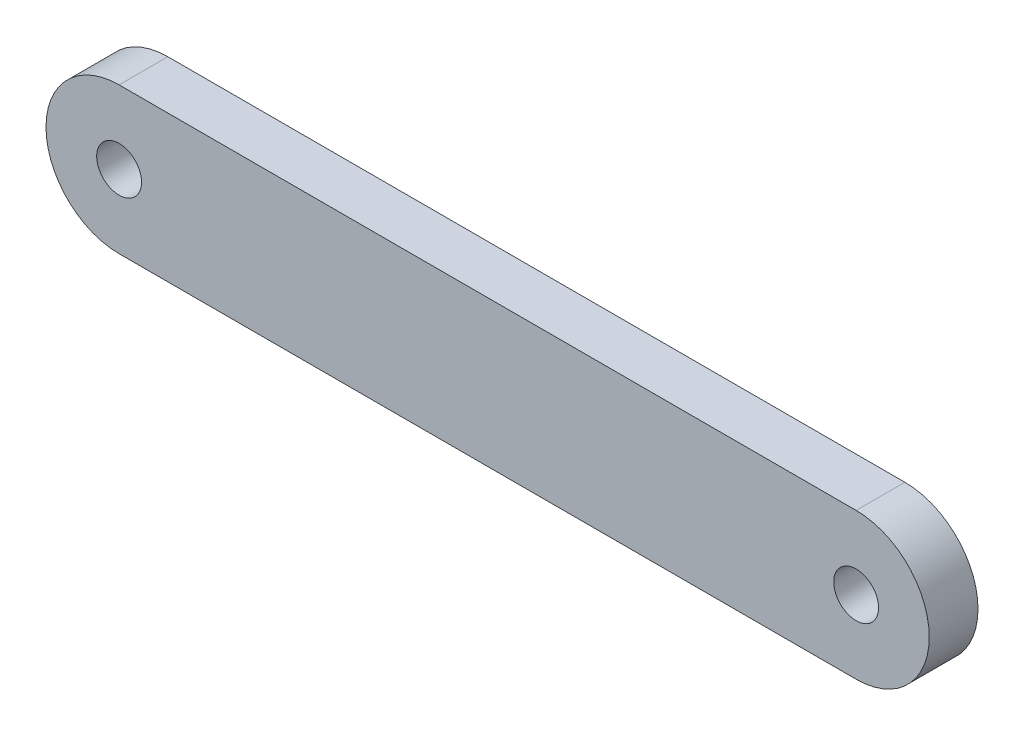
SolidWorks part; units mm, degrees
ref_plane "前视基准面" through (0, 0, 0) normal (0, 0, 1) x (1, 0, 0)
ref_plane "上视基准面" through (0, 0, 0) normal (0, 1, 0) x (1, 0, 0)
ref_plane "右视基准面" through (0, 0, 0) normal (1, 0, 0) x (0, 0, -1)
other "Configuration Table"
sketch "草图1" plane through (0, 0, 0) normal (0, 0, 1) x (1, 0, 0)
  line L1 (-37.8, 7.5) -> (37.8, 7.5)
  line L3 (-37.8, -7.5) -> (37.8, -7.5)
  line L5 (-37.8, 7.5) -> (37.8, -7.5) construction
  line L6 (-37.8, -7.5) -> (37.8, 7.5) construction
  arc A0 (-37.8, 7.5) -> (-37.8, -7.5) centre (-37.8, 0) ccw
  arc A1 (37.8, 7.5) -> (37.8, -7.5) centre (37.8, 0) cw
  circle A2 centre (-37.8, 0) radius 2.3
  circle A3 centre (37.8, 0) radius 2.3
  point P0 (0, 0)
  dimension "D1" = 4.6
  dimension "D2" = 4.6
  dimension "D3" = 75.6
  dimension "D4" = 15
extrude "凸台-拉伸1" add sketch "草图1" along normal blind 5
equation "\"fi\"=4.6"
equation "\"D1@草图1\"=\"fi\""
equation "\"D2@草图1\"=\"fi\""
equation "\"b0\"=75.6"
equation "\"D3@草图1\"=\"b2\""
equation "\"width\"=15"
equation "\"D4@草图1\"=\"width\""
equation "\"depth\"=5"
equation "\"D1@凸台-拉伸1\"=\"depth\""
equation "\"b1\"= \"b0\" *1.4/ 2'rocker"
equation "\"b2\"= \"b0\"'coupler"
equation "\"b3\"= \"b0\" / 2'coupler"
equation "\"b4\"= \"b0\" *2'leg"
equation "\"angle\"= 90度'左右cranker夹角"
